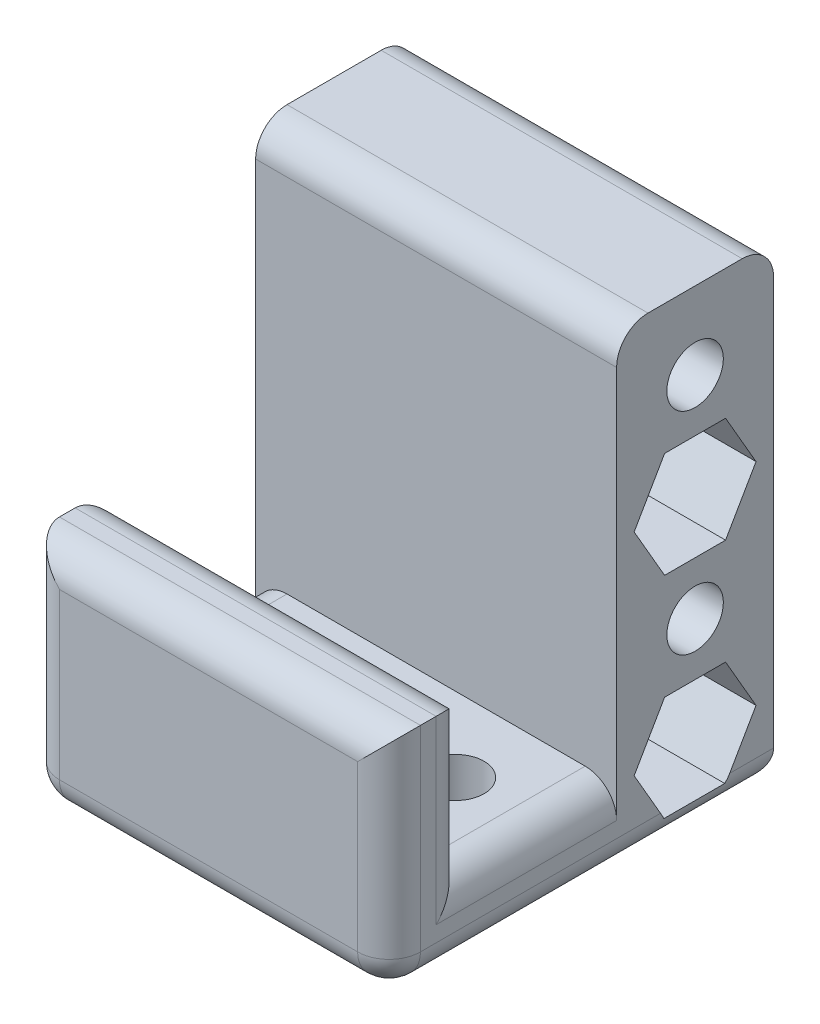
SolidWorks part; units mm, degrees
ref_plane "Front Plane" through (0, 0, 0) normal (0, 0, 1) x (1, 0, 0)
ref_plane "Top Plane" through (0, 0, 0) normal (0, 1, 0) x (1, 0, 0)
ref_plane "Right Plane" through (0, 0, 0) normal (1, 0, 0) x (0, 0, -1)
sketch "Sketch1" plane through (0, 0, 0) normal (1, 0, 0) x (0, 0, -1)
  line L0 (-12.25, -0.5) -> (-7.25, -0.5)
  line L1 (-7.25, -0.5) -> (-7.25, -10)
  line L2 (-7.25, -10) -> (2.25, -10)
  line L3 (2.25, -10) -> (2.25, 15)
  line L4 (2.25, 15) -> (12.25, 15)
  line L5 (12.25, 15) -> (12.25, -15)
  line L6 (12.25, -15) -> (-12.25, -15)
  line L7 (-12.25, -15) -> (-12.25, -0.5)
  line L8 (3.3669, 3.3629) -> (5.3084, 0)
  line L9 (5.3084, 0) -> (9.1916, 0)
  line L10 (3.3669, 10.0887) -> (5.3084, 6.7258)
  line L11 (5.3084, 6.7258) -> (9.1916, 6.7258)
  line L12 (9.1916, 6.7258) -> (11.1331, 10.0887)
  line L13 (11.1331, 10.0887) -> (9.1916, 13.4516)
  line L14 (9.1916, 13.4516) -> (5.3084, 13.4516)
  line L15 (5.3084, 13.4516) -> (3.3669, 10.0887)
  line L22 (9.1916, 0) -> (11.1331, 3.3629)
  line L23 (11.1331, 3.3629) -> (9.1916, 6.7258)
  line L24 (9.1916, 6.7258) -> (5.3084, 6.7258)
  line L25 (5.3084, 6.7258) -> (3.3669, 3.3629)
  line L26 (3.3669, -3.3629) -> (5.3084, -6.7258)
  line L27 (5.3084, -6.7258) -> (9.1916, -6.7258)
  line L28 (9.1916, -6.7258) -> (11.1331, -3.3629)
  line L29 (11.1331, -3.3629) -> (9.1916, 0)
  line L30 (9.1916, 0) -> (5.3084, 0)
  line L31 (5.3084, 0) -> (3.3669, -3.3629)
  line L32 (3.3669, -10.0887) -> (5.3084, -13.4516)
  line L33 (5.3084, -13.4516) -> (9.1916, -13.4516)
  line L34 (9.1916, -13.4516) -> (11.1331, -10.0887)
  line L35 (11.1331, -10.0887) -> (9.1916, -6.7258)
  line L36 (9.1916, -6.7258) -> (5.3084, -6.7258)
  line L37 (5.3084, -6.7258) -> (3.3669, -10.0887)
  line L38 (7.25, 10.0887) -> (7.25, 15) construction
  line L39 (7.25, 10.0887) -> (7.25, 3.3629) construction
  line L40 (7.25, 3.3629) -> (7.25, -3.3629) construction
  line L41 (7.25, -3.3629) -> (7.25, -10.0887) construction
  line L42 (7.25, -10.0887) -> (7.25, -15) construction
  circle A0 centre (7.25, 10.0887) radius 1.8
  circle A2 centre (7.25, 10.0887) radius 3.3629 construction
  circle A3 centre (7.25, 3.3629) radius 1.8
  circle A4 centre (7.25, -3.3629) radius 1.8
  circle A5 centre (7.25, -10.0887) radius 1.8
  point P2 (0, -15)
  point P9 (7.7941, -14.7566)
  point P11 (12.25, 0)
  point P14 (8.0077, -10.6369)
  point P47 (7.9979, -14.2441)
  point P49 (0, 0)
  point P50 (7.25, 15)
  dimension "D6" = 3.6
  dimension "D9" = 6.7258
  dimension "D1" = 5
  dimension "D2" = 9.5
  dimension "D3" = 5
  dimension "D4" = 10
  dimension "D5" = 30
  dimension "D7" = 4
extrude "Boss-Extrude1" add sketch "Sketch1" along normal mid plane 23 contours L37 L26 L31 L8 L25 L10 L15 L14 L13 L5 L4 L3 L2 L1 L0 L7 L6 L34 L33 L32 | L27 L37 L32 L33 L34 L35 A5 | L9 L31 L26 L27 L28 L29 A4 | L11 L25 L8 L9 L22 L23 A3 | L14 L15 L10 L11 L12 L13 A0 | L23 L5 L12 | L29 L5 L22 | L35 L5 L28 region at (0, -0.8873, 9.75) region at (0, 4.993, -4.4266) region at (0, -0.1027, -7.25) region at (0, 8.4586, -4.4266) region at (0, -6.8285, -7.25)
extrude "Cut-Extrude1" cut sketch "Sketch1<3>" against normal through all from offset 5 contours L14 L15 L10 L11 L12 L13 A0 | L9 L31 L26 L27 L28 L29 A4 region at (0, -0.1027, -7.25) region at (0, 8.4586, -4.4266) offset against normal yes
sketch "Sketch1<3>" plane through (0, 0, 0) normal (1, 0, 0) x (0, 0, -1) same geometry as "Sketch1"
extrude "Cut-Extrude2" cut sketch "Sketch1<4>" along normal through all from offset 5 contours L11 L25 L8 L9 L22 L23 A3 | L27 L37 L32 L33 L34 L35 A5 region at (0, 4.993, -4.4266) region at (0, -6.8285, -7.25)
sketch "Sketch1<4>" plane through (0, 0, 0) normal (1, 0, 0) x (0, 0, -1) same geometry as "Sketch1"
sketch "Sketch2" plane through (0, 0, 0) normal (0, 1, 0) x (1, 0, 0)
  line L0 (-6, -2.5) -> (6, -2.5) construction
  line L1 (11.5, -7.25) -> (11.5, 2.25) construction
  circle A0 centre (-6, -2.5) radius 1.8
  circle A1 centre (6, -2.5) radius 1.8
  point P4 (0, -2.5)
  point P8 (11.5, -2.5)
  dimension "D1" = 3.6
  dimension "D2" = 12
extrude "Cut-Extrude3" cut sketch "Sketch2" against normal through all both and the other way through all
fillet "Fillet1" radius 2 14 edges at (-11.5, -10, 2.5) (11.5, -10, 2.5) (11.5, -5.25, 7.25) (-11.5, -5.25, 7.25) (-11.5, -15, 0) (-11.5, -7.75, 12.25) (11.5, -15, 0) (11.5, -7.75, 12.25) (0, 15, -2.25) (0, 15, -12.25) (0, -15, -12.25) (0, -15, 12.25) (0, -0.5, 7.25) (0, -0.5, 12.25)
